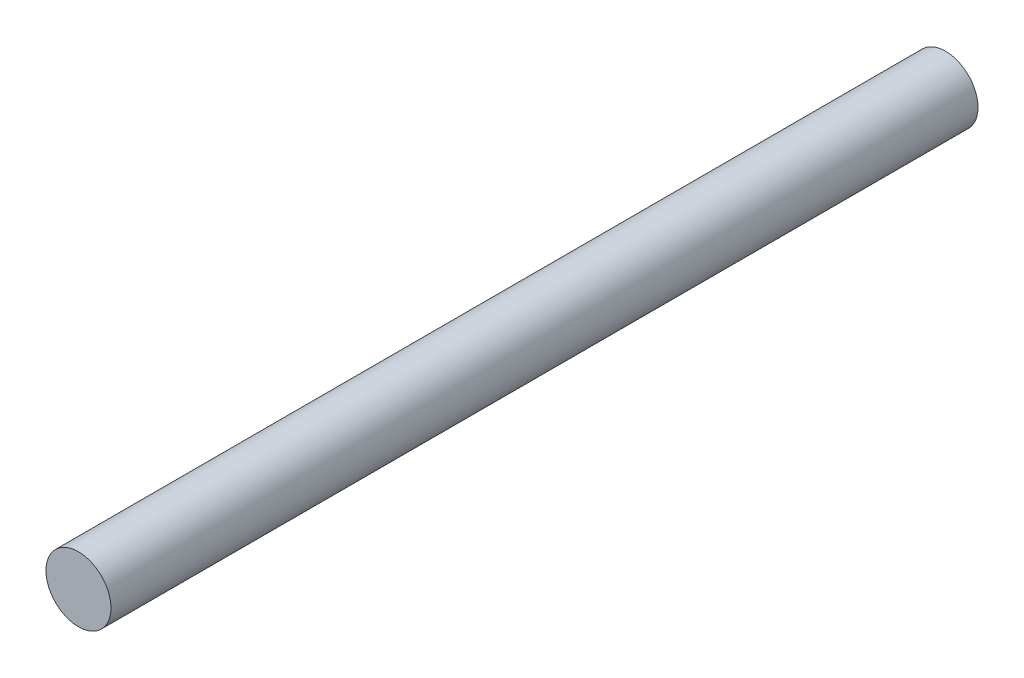
SolidWorks part; units mm, degrees
ref_plane "Front Plane" through (0, 0, 0) normal (0, 0, 1) x (1, 0, 0)
ref_plane "Top Plane" through (0, 0, 0) normal (0, 1, 0) x (1, 0, 0)
ref_plane "Right Plane" through (0, 0, 0) normal (1, 0, 0) x (0, 0, -1)
sketch "Sketch1" plane through (0, 0, 0) normal (0, 0, 1) x (1, 0, 0)
  circle A0 centre (0, 0) radius 1.905
  dimension "D1" = 3.81
extrude "Boss-Extrude1" add sketch "Sketch1" along normal blind 50.8
